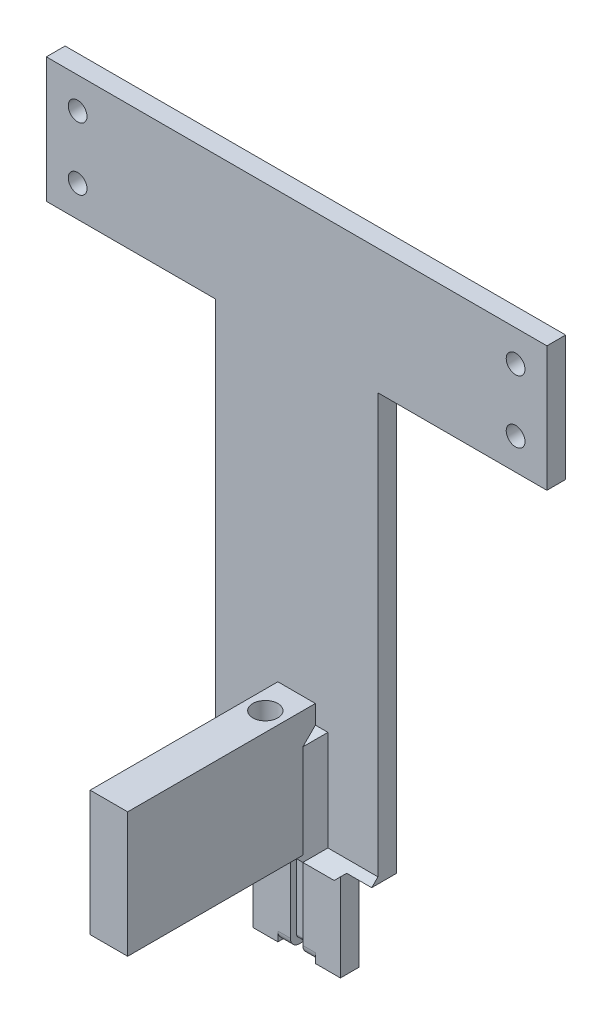
SolidWorks part; units mm, degrees
ref_plane "前视基准面" through (0, 0, 0) normal (0, 0, 1) x (1, 0, 0)
ref_plane "上视基准面" through (0, 0, 0) normal (0, 1, 0) x (1, 0, 0)
ref_plane "右视基准面" through (0, 0, 0) normal (1, 0, 0) x (0, 0, -1)
other "Configuration Table"
sketch "草图1" plane through (0, 0, 0) normal (0, 0, 1) x (1, 0, 0)
  line L1 (0, 0) -> (-80, 0)
  line L2 (0, 0) -> (0, 20)
  line L3 (0, 20) -> (-80, 20)
  line L4 (-80, 0) -> (-80, 20)
  dimension "D1" = 80
  dimension "D2" = 20
extrude "凸台-拉伸1" add sketch "草图1" along normal blind 3
sketch "草图2" plane through (0, 0, 3) normal (0, 0, 1) x (1, 0, 0)
  line L0 (0, 20) -> (-80, 20) construction
  line L1 (-37, 20) -> (-43, 20)
  line L2 (-40, 20) -> (-40, 0) construction
  line L3 (-37, 0) -> (-43, 0)
  line L4 (-43, 20) -> (-43, 0)
  line L6 (-37, 20) -> (-37, 0)
  dimension "D1" = 6
extrude "凸台-拉伸2" add sketch "草图2" along normal blind 95
sketch "草图3" plane through (0, 0, 0) normal (0, -1, 0) x (1, 0, 0)
  line L0 (-37, 98) -> (-37, 3) construction
  line L1 (-43, 98) -> (-37, 98)
  line L2 (-43, 98) -> (-43, 83)
  line L3 (-43, 83) -> (-37, 83)
  line L4 (-37, 98) -> (-37, 83)
  dimension "D1" = 15
extrude "凸台-拉伸3" add sketch "草图3" along normal blind 80
chamfer "倒角1" distance 10 angle 45 2 edges at (-43, 10, 3) (-37, 10, 3)
chamfer "倒角2" distance 10 angle 45 1 edges at (-40, 0, 83)
fillet "圆角1" radius 10 1 edges at (-40, 20, 98)
sketch "草图4" plane through (0, 0, 83) normal (0, 0, -1) x (-1, 0, 0)
  line L0 (37, -80) -> (37, -10) construction
  line L1 (43, -80) -> (37, -80)
  line L2 (43, -80) -> (43, -65)
  line L3 (43, -65) -> (37, -65)
  line L4 (37, -80) -> (37, -65)
  dimension "D1" = 15
extrude "凸台-拉伸4" add sketch "草图4" along normal blind 5
sketch "草图5" plane through (0, 0, 98) normal (0, 0, 1) x (1, 0, 0)
  line L4 (-43, -65) -> (-43, -80)
  line L5 (-37, -65) -> (-43, -65)
  line L6 (-37, -80) -> (-37, -65)
  line L7 (-43, -80) -> (-37, -80)
  line L8 (-43, -65) -> (-43, -80)
  line L9 (-37, -65) -> (-43, -65)
  line L10 (-37, -80) -> (-37, -65)
  line L11 (-43, -80) -> (-37, -80)
  dimension "D1" = 0
extrude "凸台-拉伸5" add sketch "草图5" along normal blind 5
fillet "圆角2" radius 2 2 edges at (-40, -65, 78) (-40, -65, 103)
chamfer "倒角3" distance 3 angle 45 2 edges at (-40, -65, 83) (-40, -65, 98)
sketch "草图6" plane through (0, 0, 0) normal (0, -1, 0) x (1, 0, 0)
  line L0 (-40, 73) -> (-40, 8) construction
  line L1 (-37, 73) -> (-43, 73) construction
  line L2 (-40, 8) -> (-40, 23) construction
  circle A0 centre (-40, 8) radius 1.5
  circle A1 centre (-40, 23) radius 1.5
  dimension "D2" = 3
  dimension "D4" = 3
  dimension "D1" = 65
  dimension "D3" = 15
extrude "切除-拉伸1" cut sketch "草图6" against normal blind 30
sketch "草图7" plane through (0, 0, 0) normal (0, -1, 0) x (1, 0, 0)
  line L0 (-80, 0) -> (0, 0) construction
  line L1 (-53, 3) -> (-27, 3)
  line L2 (-53, 3) -> (-53, 0)
  line L3 (-53, 0) -> (-27, 0)
  line L4 (-27, 3) -> (-27, 0)
  dimension "D1" = 26
extrude "凸台-拉伸6" add sketch "草图7" along normal offset from surface (68 mm away) 12 up to face at (-40, -80, 90.5)
chamfer "倒角4" distance 10 angle 45 2 edges at (-53, -68, 1.5) (-27, -68, 1.5)
sketch "草图8" plane through (0, 0, 3) normal (0, 0, 1) x (1, 0, 0)
  line L4 (-37, -80) -> (-37, -67)
  line L5 (-37, -67) -> (-43, -67)
  line L6 (-43, -67) -> (-43, -80)
  line L7 (-43, -80) -> (-37, -80)
  line L8 (-37, -80) -> (-37, -67)
  line L9 (-37, -67) -> (-43, -67)
  line L10 (-43, -67) -> (-43, -80)
  line L11 (-43, -80) -> (-37, -80)
  dimension "D1" = 0
extrude "凸台-拉伸7" add sketch "草图8" along normal blind 100
chamfer "倒角5" distance 5 angle 45 1 edges at (-40, -67, 3)
chamfer "倒角6" distance 2 angle 45 2 edges at (-37, -65, 3) (-43, -65, 3)
sketch "草图9" plane through (0, 20, 0) normal (0, 1, 0) x (1, 0, 0)
  line L1 (-80, -3) -> (19.5327, -3)
  line L2 (-80, -3) -> (-80, -107.0773)
  line L3 (-80, -107.0773) -> (19.5327, -107.0773)
  line L4 (19.5327, -3) -> (19.5327, -107.0773)
extrude "切除-拉伸3" cut sketch "草图9" against normal blind 30
sketch "草图14" plane through (0, -10, 0) normal (0, 1, 0) x (1, 0, 0)
  line L1 (-46.7237, -54.1452) -> (-31.1304, -54.1452)
  line L2 (-46.7237, -54.1452) -> (-46.7237, -107.9349)
  line L3 (-46.7237, -107.9349) -> (-31.1304, -107.9349)
  line L4 (-31.1304, -54.1452) -> (-31.1304, -107.9349)
extrude "切除-拉伸5" cut sketch "草图14" against normal up to surface (57 mm away) up to face at (-40, -67, 43)
sketch "草图15" plane through (0, -67, 0) normal (0, 1, 0) x (1, 0, 0)
  line L0 (-43, -103) -> (-43, -8) construction
  line L1 (-37, -103) -> (-43, -103)
  line L2 (-37, -103) -> (-37, -78)
  line L3 (-37, -78) -> (-43, -78)
  line L4 (-43, -103) -> (-43, -78)
  dimension "D1" = 25
extrude "凸台-拉伸8" add sketch "草图15" along normal blind 5
sketch "草图16" plane through (0, -80, 0) normal (0, -1, 0) x (1, 0, 0)
  line L4 (-37, 78) -> (-37, 103)
  line L5 (-43, 78) -> (-37, 78)
  line L6 (-43, 103) -> (-43, 78)
  line L7 (-37, 103) -> (-43, 103)
  line L8 (-37, 78) -> (-37, 103)
  line L9 (-43, 78) -> (-37, 78)
  line L10 (-43, 103) -> (-43, 78)
  line L11 (-37, 103) -> (-43, 103)
  dimension "D1" = 0
extrude "凸台-拉伸9" add sketch "草图16" along normal blind 5
chamfer "倒角7" distance 5 angle 45 2 edges at (-40, -80, 78) (-40, -67, 78)
sketch "草图17" plane through (0, 0, 103) normal (0, 0, 1) x (1, 0, 0)
  line L4 (-37, -85) -> (-37, -62)
  line L5 (-37, -62) -> (-43, -62)
  line L6 (-43, -62) -> (-43, -85)
  line L7 (-43, -85) -> (-37, -85)
  line L8 (-37, -85) -> (-37, -62)
  line L9 (-37, -62) -> (-43, -62)
  line L10 (-43, -62) -> (-43, -85)
  line L11 (-43, -85) -> (-37, -85)
  dimension "D1" = 0
extrude "切除-拉伸6" cut sketch "草图17" against normal up to surface (100 mm away) up to face at (-40, -27.6667, 3)
sketch "草图20" plane through (0, 20, 0) normal (0, 1, 0) x (1, 0, 0)
  line L0 (0, -3) -> (-80, -3) construction
  line L1 (-51.2861, -3) -> (-24.5869, -3)
  line L2 (-51.2861, -3) -> (-51.2861, -7.006)
  line L3 (-51.2861, -7.006) -> (-24.5869, -7.006)
  line L4 (-24.5869, -3) -> (-24.5869, -7.006)
extrude "切除-拉伸7" cut sketch "草图20" against normal blind 133
sketch "草图21" plane through (0, 0, 3) normal (0, 0, 1) x (1, 0, 0)
  line L1 (-43, -68) -> (-37, -68)
  line L2 (-43, -68) -> (-43, -53)
  line L3 (-43, -53) -> (-37, -53)
  line L4 (-37, -68) -> (-37, -53)
  dimension "D1" = 15
extrude "凸台-拉伸11" add sketch "草图21" along normal blind 30
sketch "草图22" plane through (0, -53, 0) normal (0, 1, 0) x (1, 0, 0)
  line L1 (-37, -33) -> (-43, -33) construction
  line L2 (-43, -33) -> (-43, -3) construction
  circle A0 centre (-40, -8) radius 2
  dimension "D2" = 4
  dimension "D4" = 25
  dimension "D6" = 3
extrude "切除-拉伸8" cut sketch "草图22" against normal blind 27
sketch "草图24" plane through (0, 0, 0) normal (0, 0, -1) x (-1, 0, 0)
  line L0 (43, -68) -> (53, -58) construction
  line L2 (27, -58) -> (27, -68)
  line L6 (53, -58) -> (53, -68)
  line L7 (53, -68) -> (43, -68)
  line L9 (27, -58) -> (37, -68) construction
  line L10 (43, -68) -> (53, -58)
  line L11 (27, -58) -> (37, -68)
  line L12 (27, -68) -> (37, -68)
extrude "凸台-拉伸12" add sketch "草图24" against normal up to surface (3 mm away) up to face at (-40, -26.5, 3)
sketch "草图26" plane through (0, -68, 0) normal (0, -1, 0) x (1, 0, 0)
  line L0 (-53, 0) -> (-27, 0) construction
  line L1 (-43, 3) -> (-47, 3)
  line L2 (-43, 3) -> (-43, 0)
  line L3 (-43, 0) -> (-47, 0)
  line L4 (-47, 3) -> (-47, 0)
  line L6 (-37, 3) -> (-33, 3)
  line L7 (-37, 3) -> (-37, 0)
  line L8 (-37, 0) -> (-33, 0)
  line L9 (-33, 3) -> (-33, 0)
  dimension "D1" = 4
  dimension "D2" = 4
extrude "凸台-拉伸14" add sketch "草图26" along normal blind 16
sketch "草图27" plane through (0, 0, 3) normal (0, 0, 1) x (1, 0, 0)
  line L12 (-47, -84) -> (-47, -68) construction
  line L13 (-47, -69) -> (-43, -69)
  line L14 (-47, -69) -> (-47, -82)
  line L15 (-47, -82) -> (-43, -82)
  line L16 (-43, -69) -> (-43, -82)
  line L17 (-43, -84) -> (-43, -68) construction
  line L18 (-37, -84) -> (-37, -68) construction
  line L19 (-37, -69) -> (-33, -69)
  line L20 (-37, -69) -> (-37, -82)
  line L21 (-37, -82) -> (-33, -82)
  line L22 (-33, -69) -> (-33, -82)
  line L23 (-33, -84) -> (-33, -68) construction
  line L24 (-27, -68) -> (-33, -68) construction
  line L25 (-47, -68) -> (-53, -68) construction
  line L26 (-43, -84) -> (-47, -84) construction
  line L27 (-33, -84) -> (-37, -84) construction
  dimension "D1" = 1
  dimension "D2" = 1
  dimension "D3" = 2
  dimension "D4" = 2
extrude "凸台-拉伸21" add sketch "草图27" along normal blind 6
sketch "草图28" plane through (-33, 0, 0) normal (1, 0, 0) x (0, 0, -1)
  line L0 (-6, -69) -> (-6, -75.5) construction
  line L1 (-9, -69) -> (-3, -69) construction
  circle A0 centre (-6, -75.5) radius 1.5
  dimension "D2" = 3
  dimension "D1" = 6.5
extrude "切除-拉伸9" cut sketch "草图28" against normal blind 22
chamfer "倒角8" distance 2 angle 45 6 edges at (-30, -68, 3) (-50, -68, 3) (-47, -68.5, 3) (-45, -69, 3) (-33, -68.5, 3) (-35, -69, 3)
chamfer "倒角9" distance 2 angle 45 7 edges at (-43, -60, 3) (-40, -53, 3) (-37, -60, 3) (-37, -67.5, 3.5) (-43, -67.5, 3.5) (-37, -68.5, 4.5) (-43, -68.5, 4.5)
chamfer "倒角10" distance 2 angle 45 2 edges at (-47, -68, 2) (-33, -68, 2)
chamfer "倒角11" distance 1 angle 45 4 edges at (-43, -68, 2.5) (-37, -68, 2.5) (-37, -68.5, 5) (-43, -68.5, 5)
sketch "草图29" plane through (0, -53, 0) normal (0, 1, 0) x (1, 0, 0)
  line L4 (-37, -33) -> (-37, -5)
  line L5 (-37, -5) -> (-43, -5)
  line L6 (-43, -5) -> (-43, -33)
  line L7 (-43, -33) -> (-37, -33)
  line L8 (-37, -33) -> (-37, -5)
  line L9 (-37, -5) -> (-43, -5)
  line L10 (-43, -5) -> (-43, -33)
  line L11 (-43, -33) -> (-37, -33)
  dimension "D1" = 0
extrude "凸台-拉伸22" add sketch "草图29" along normal blind 20
sketch "草图30" plane through (0, 0, 5) normal (0, 0, -1) x (-1, 0, 0)
  line L4 (37, -53) -> (43, -53)
  line L5 (43, -53) -> (43, -33)
  line L6 (43, -33) -> (37, -33)
  line L7 (37, -33) -> (37, -53)
  line L8 (37, -53) -> (43, -53)
  line L9 (43, -53) -> (43, -33)
  line L10 (43, -33) -> (37, -33)
  line L11 (37, -33) -> (37, -53)
  dimension "D1" = 0
extrude "凸台-拉伸23" add sketch "草图30" along normal up to surface (2 mm away) up to face at (-45, -83, 3)
sketch "草图31" plane through (0, -53, 0) normal (0, -1, 0) x (1, 0, 0)
  circle A1 centre (-40, 8) radius 2
  circle A2 centre (-40, 8) radius 2
  dimension "D1" = 0
extrude "切除-拉伸10" cut sketch "草图31" against normal up to surface (20 mm away)
sketch "草图32" plane through (0, 0, 3) normal (0, 0, 1) x (1, 0, 0)
  line L0 (-80, 20) -> (-75, 20) construction
  line L1 (0, 20) -> (-80, 20) construction
  line L2 (-75, 20) -> (-75, 15) construction
  line L3 (-80, 0) -> (-75, 0) construction
  line L4 (-80, 0) -> (-53, 0) construction
  line L5 (-75, 0) -> (-75, 5) construction
  line L6 (-40, 20) -> (-40, 2.4028) construction
  circle A0 centre (-75, 15) radius 1.5
  circle A1 centre (-75, 5) radius 1.5
  circle A2 centre (-5, 5) radius 1.5
  circle A3 centre (-5, 15) radius 1.5
  dimension "D5" = 3
  dimension "D6" = 3
  dimension "D1" = 5
  dimension "D2" = 5
  dimension "D3" = 5
  dimension "D4" = 5
extrude "切除-拉伸11" cut sketch "草图32" against normal blind 10
sketch "草图33" plane through (0, -33, 0) normal (0, 1, 0) x (1, 0, 0)
  line L4 (-43, -33) -> (-37, -33)
  line L5 (-37, -33) -> (-37, -3)
  line L6 (-37, -3) -> (-43, -3)
  line L7 (-43, -3) -> (-43, -33)
  line L8 (-43, -33) -> (-37, -33)
  line L9 (-37, -33) -> (-37, -3)
  line L10 (-37, -3) -> (-43, -3)
  line L11 (-43, -3) -> (-43, -33)
  dimension "D1" = 0
extrude "切除-拉伸12" cut sketch "草图33" against normal blind 15
sketch "草图34" plane through (0, 0, 9) normal (0, 0, 1) x (1, 0, 0)
  line L1 (-37, -82) -> (-33, -82) construction
  line L2 (-33, -82) -> (-33, -70) construction
  line L3 (-33, -70) -> (-32, -69) construction
  line L4 (-32, -69) -> (-37, -69) construction
  line L5 (-43, -69) -> (-48, -69) construction
  line L6 (-48, -69) -> (-47, -70) construction
  line L7 (-47, -70) -> (-47, -82) construction
  line L8 (-47, -82) -> (-43, -82) construction
  line L11 (-37, -82) -> (-33, -82)
  line L12 (-33, -82) -> (-33, -70)
  line L13 (-33, -70) -> (-32, -69)
  line L14 (-32, -69) -> (-37, -69)
  line L15 (-43, -69) -> (-48, -69)
  line L16 (-48, -69) -> (-47, -70)
  line L17 (-47, -70) -> (-47, -82)
  line L18 (-47, -82) -> (-43, -82)
  line L21 (-43, -69) -> (-37, -69)
  line L23 (-43, -82) -> (-37, -82)
extrude "切除-拉伸13" cut sketch "草图34" against normal up to surface (6 mm away) up to face at (-45, -83, 3)
sketch "草图36" plane through (-43, 0, 0) normal (1, 0, 0) x (0, 0, -1)
  line L0 (-1.5, -84) -> (-1.5, -82.5) construction
  line L1 (0, -84) -> (-3, -84) construction
  line L2 (-3, -82.5) -> (0, -82.5)
  arc A0 (-3, -82.5) -> (0, -82.5) centre (-1.5, -82.5) ccw
  dimension "D1" = 1.5
extrude "凸台-拉伸24" add sketch "草图36" along normal blind 2
sketch "草图37" plane through (0, -82.5, 0) normal (0, 1, 0) x (1, 0, 0)
  line L4 (-41, -3) -> (-41, 0)
  line L5 (-41, 0) -> (-43, 0)
  line L6 (-43, 0) -> (-43, -3)
  line L7 (-43, -3) -> (-41, -3)
  line L9 (-41, 0) -> (-43, 0)
  line L10 (-43, 0) -> (-43, -3)
  line L11 (-43, -3) -> (-41, -3)
  line L12 (-41, -3) -> (-41, 0)
  dimension "D1" = 0
extrude "凸台-拉伸25" add sketch "草图37" along normal up to next
sketch "草图38" plane through (-41, 0, 0) normal (1, 0, 0) x (0, 0, -1)
  line L0 (-3, -84) -> (-1.5, -84) construction
  line L1 (-1.5, -84) -> (-1.5, -82.5) construction
  line L2 (-2, -82.5) -> (-1, -82.5)
  arc A0 (-2, -82.5) -> (-1, -82.5) centre (-1.5, -82.5) ccw
  dimension "D2" = 1
  dimension "D1" = 1.5
extrude "凸台-拉伸26" add sketch "草图38" along normal blind 2
sketch "草图39" plane through (-39, 0, 0) normal (1, 0, 0) x (0, 0, -1)
  line L0 (-3, -82.5) -> (0, -82.5)
  arc A0 (-3, -82.5) -> (0, -82.5) centre (-1.5, -82.5) ccw construction
  arc A1 (-3, -82.5) -> (0, -82.5) centre (-1.5, -82.5) ccw
extrude "凸台-拉伸27" add sketch "草图39" along normal blind 2
sketch "草图40" plane through (0, -82.5, 0) normal (0, 1, 0) x (1, 0, 0)
  line L8 (-41, -1) -> (-41, -2)
  line L9 (-41, -2) -> (-39, -2)
  line L10 (-39, -2) -> (-39, -3)
  line L11 (-39, -3) -> (-37, -3)
  line L12 (-37, -3) -> (-37, 0)
  line L13 (-37, 0) -> (-39, 0)
  line L14 (-39, 0) -> (-39, -1)
  line L15 (-39, -1) -> (-41, -1)
  line L16 (-41, -1) -> (-41, -2)
  line L17 (-41, -2) -> (-39, -2)
  line L18 (-39, -2) -> (-39, -3)
  line L19 (-39, -3) -> (-37, -3)
  line L20 (-37, -3) -> (-37, 0)
  line L21 (-37, 0) -> (-39, 0)
  line L22 (-39, 0) -> (-39, -1)
  line L23 (-39, -1) -> (-41, -1)
  dimension "D1" = 0
extrude "凸台-拉伸28" add sketch "草图40" along normal up to next
chamfer "倒角12" distance 1 angle 45 3 edges at (-40, -68, 0) (-41, -68, 0.5) (-39, -68, 0.5)
